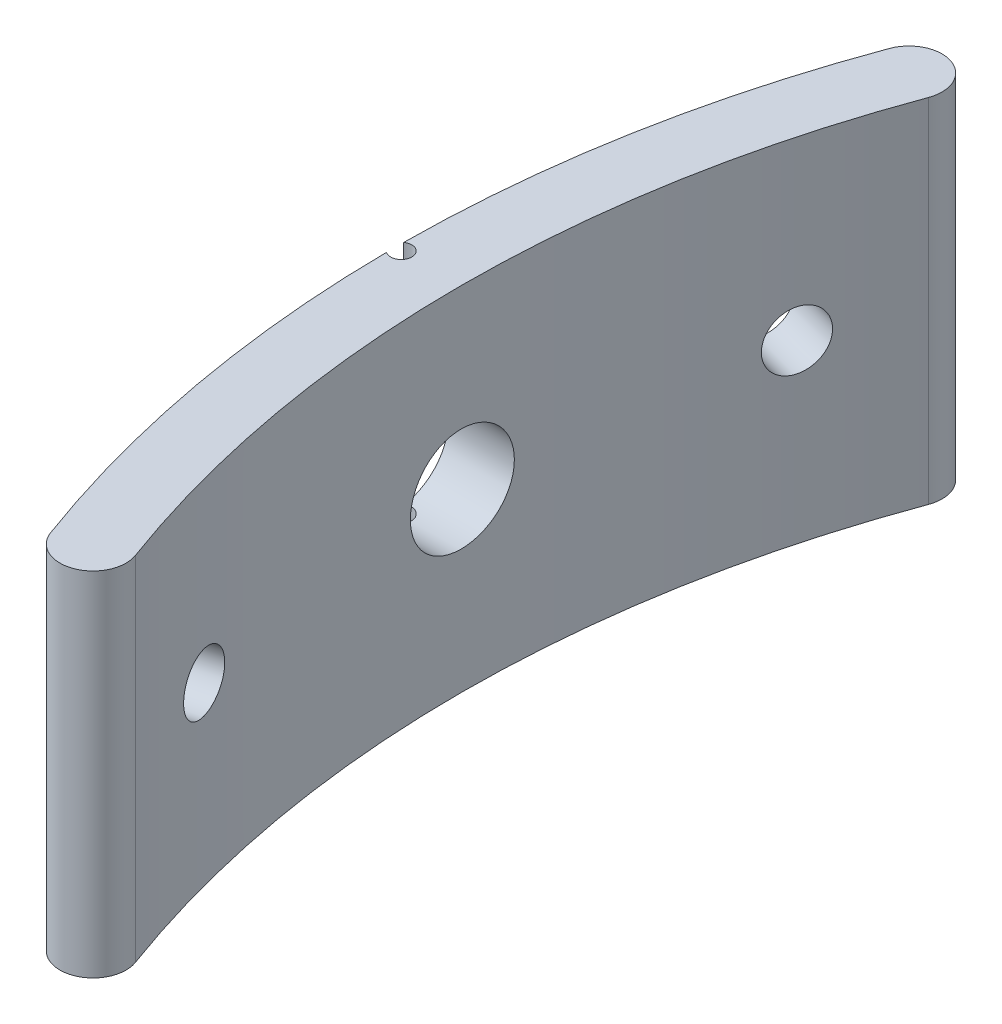
SolidWorks part; units mm, degrees
ref_plane "Front Plane" through (0, 0, 0) normal (0, 0, 1) x (1, 0, 0)
ref_plane "Top Plane" through (0, 0, 0) normal (0, 1, 0) x (1, 0, 0)
ref_plane "Right Plane" through (0, 0, 0) normal (1, 0, 0) x (0, 0, -1)
sketch "REFERENCE" plane through (0, 0, 0) normal (0, 1, 0) x (1, 0, 0)
  circle A0 centre (0, 0) radius 65 construction
  circle A1 centre (0, 0) radius 70 construction
  dimension "D1" = 130
  dimension "D2" = 140
sketch "Sketch3" plane through (0, 0, 0) normal (0, 1, 0) x (1, 0, 0)
  line L0 (-60.9816, 22.5) -> (-60.9816, -22.5) construction
  line L1 (-60.9816, 22.5) -> (-64.4997, 23.7981) construction
  line L2 (-60.9816, -22.5) -> (-64.4997, -23.7981) construction
  arc A0 (-60.9816, 22.5) -> (-60.9816, -22.5) centre (0, 0) ccw
  circle A7 centre (0, 0) radius 65 construction
  circle A8 centre (0, 0) radius 68.75 construction
  arc A9 (-64.4997, -23.7981) -> (-60.9816, -22.5) centre (-62.7406, -23.149) ccw
  arc A10 (-60.9816, 22.5) -> (-64.4997, 23.7981) centre (-62.7406, 23.149) ccw
  arc A11 (-64.4997, 23.7981) -> (-64.4997, -23.7981) centre (0, 0) ccw
  dimension "D2" = 137.5
  dimension "D1" = 45
extrude "Boss-Extrude2" add sketch "Sketch3" along normal mid plane 20
ref_axis "Axis1" through (0, 64.8029, 0) along (0, -1, 0)
ref_plane "Plane1" through (-62.7852, 0, -16.8232) normal (0.9659, 0, 0.2588) x (0, -1, 0)
sketch "Sketch9" plane through (-62.7852, 0, -16.8232) normal (0.9659, 0, 0.2588) x (0, -1, 0)
  circle A0 centre (0, 0) radius 1.65
  dimension "D1" = 3.3
extrude "Cut-Extrude3" cut sketch "Sketch9" against normal mid plane 20
mirror "Mirror1" about plane through (0, 0, 0) normal (0, 0, 1) of "Cut-Extrude3"
sketch "Sketch10" plane through (0, 0, 0) normal (1, 0, 0) x (0, 0, -1)
  circle A0 centre (0, 0) radius 2.95
  dimension "D1" = 5.9
extrude "Cut-Extrude4" cut sketch "Sketch10" against normal through all contours A0
ref_plane "Plane3" through (-67.6148, 0, -18.1173) normal (0.9659, 0, 0.2588) x (0, -1, 0)
sketch "Sketch12" plane through (-67.6148, 0, -18.1173) normal (0.9659, 0, 0.2588) x (0, -1, 0)
  circle A0 centre (0, 0) radius 3
  dimension "D1" = 6
extrude "Cut-Extrude5" cut sketch "Sketch12" along normal blind 2
mirror "Mirror2" about plane through (0, 0, 0) normal (0, 0, 1) of "Cut-Extrude5"
ref_plane "Plane4" through (-68.75, 0, 0) normal (1, 0, 0) x (0, 0, -1)
sketch "Sketch13" plane through (0, 10, 0) normal (0, 1, 0) x (1, 0, 0)
  line L0 (-11, 0) -> (11, 0) construction
  line L2 (-68.75, -11) -> (-68.75, 11) construction
  circle A0 centre (-68.4, 0) radius 0.6
  point P4 (0, 0)
  dimension "D1" = 1.2
  dimension "D2" = 0.25
extrude "Cut-Extrude6" cut sketch "Sketch13" against normal through all
